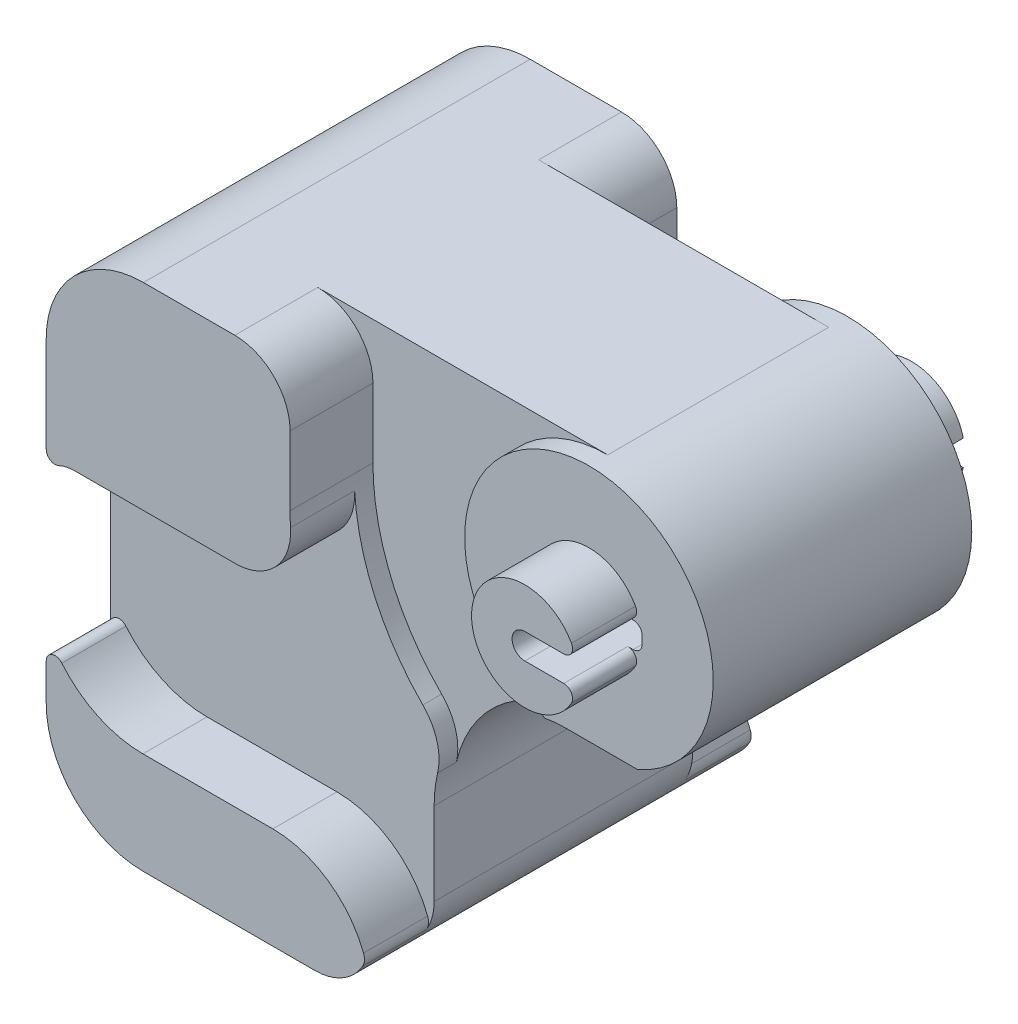
SolidWorks part; units mm, degrees
material "ABS"
ref_plane "Front Plane" through (0, 0, 0) normal (0, 0, 1) x (1, 0, 0)
ref_plane "Top Plane" through (0, 0, 0) normal (0, 1, 0) x (1, 0, 0)
ref_plane "Right Plane" through (0, 0, 0) normal (1, 0, 0) x (0, 0, -1)
sketch "Sketch1" plane through (0, 0, 0) normal (0, 0, 1) x (1, 0, 0)
  line L0 (5.5562, 0) -> (16.6687, 0)
  line L1 (0, 5.5562) -> (22.225, 5.5562)
  line L4 (22.225, 5.5562) -> (22.225, -5.5562) construction
  line L5 (0, 5.5562) -> (22.225, 5.5562) construction
  line L9 (13.1316, 0.7956) -> (22.225, 0) construction
  line L10 (22.225, 0) -> (22.225, -9.1281) construction
  line L11 (5.5562, 0) -> (0, 0)
  line L12 (0, 0) -> (0, 5.5562)
  line L13 (13.7542, 7.9121) -> (13.1316, 0.7956) construction
  circle A0 centre (0, 0) radius 5.5562 construction
  circle A1 centre (22.225, 0) radius 5.5562 construction
  circle A2 centre (22.225, -9.1281) radius 3.5719
  arc A3 (22.225, -5.5562) -> (22.225, 5.5562) centre (22.225, 0) ccw
  circle A5 centre (22.225, 0) radius 1.7859
  circle A6 centre (22.225, -9.1281) radius 1.7859
  arc A7 (16.6687, 0) -> (22.225, -5.5562) centre (22.225, 0) ccw
  circle A23 centre (22.225, 0) radius 9.1281 construction
  circle A30 centre (2.7781, 2.7781) radius 2.7781
  circle A31 centre (0.8137, 4.7426) radius 0.8137
  circle A32 centre (13.1316, 0.7956) radius 1.7859
  circle A33 centre (13.1316, 0.7956) radius 3.5719
  circle A34 centre (13.7542, 7.9121) radius 1.7859
  circle A35 centre (13.7542, 7.9121) radius 3.5719
  arc A36 (14.9108, 0.6399) -> (22.225, -7.3422) centre (22.225, 0) ccw
  arc A37 (22.225, -10.9141) -> (11.3525, 0.9512) centre (22.225, 0) cw
  arc A38 (22.225, -12.7) -> (9.5733, 1.1069) centre (22.225, 0) cw
  dimension "D1" = 22.225
  dimension "D2" = 11.1125
  dimension "D3" = 3.5719
  dimension "D5" = 7.1437
  dimension "D4" = 95
sketch "Sketch3" plane through (0, 0, 0) normal (0, 0, 1) x (1, 0, 0)
  line L0 (0.8137, 5.5562) -> (11.0694, 5.5562)
  line L1 (0, 5.5562) -> (22.225, 5.5562) construction
  line L2 (0, 5.5562) -> (0, 0)
  line L3 (0, 0) -> (9.6495, 0)
  line L4 (5.5562, 0) -> (16.6687, 0) construction
  line L5 (13.1316, 4.6214) -> (15.1433, 4.6214)
  line L7 (0, 0) -> (0, -3.175)
  line L8 (0, -3.175) -> (9.6495, -3.175)
  line L9 (9.6495, -3.175) -> (9.6495, 0)
  line L10 (0, 5.5562) -> (0.8137, 5.5562)
  line L11 (0, 5.5562) -> (0, 11.484)
  line L12 (0, 11.484) -> (13.7542, 11.484)
  line L13 (9.3057, 0.7956) -> (9.3057, -3.175)
  circle A0 centre (13.1316, 0.7956) radius 3.5719
  circle A1 centre (13.7542, 7.9121) radius 3.5719
  circle A2 centre (13.7542, 7.9121) radius 1.5321
  circle A3 centre (13.1316, 0.7956) radius 3.5719 construction
  circle A5 centre (13.7542, 7.9121) radius 3.5719 construction
  circle A6 centre (0.8137, 4.7426) radius 0.8137 construction
  circle A9 centre (13.1316, 0.7956) radius 3.8259
  arc A11 (9.5733, 1.1069) -> (9.6495, -1.7736) centre (22.225, 0) ccw
  dimension "D2" = 3.0643
  dimension "D3" = 0.254
  dimension "D1" = 3.175
extrude "Boss-Extrude1" add sketch "Sketch3" along normal blind 5.5562 contours A1 L12 L11 L10 L0 | A2 | A9 L5 A1 A2 | A9 A1 L0 L10 L2 L3 L13 | L13 L3 L7 L8 region at (5.3993, 8.5885, 0) region at (5.1753, 2.918, 0) region at (10.5911, 9.3448, 0) region at (4.6529, -1.5875, 0) region at (13.7542, 7.9121, 0)
sketch "Sketch5" plane through (0, 0, 5.5562) normal (0, 0, 1) x (1, 0, 0)
  line L0 (13.7542, 11.484) -> (0, 11.484)
  line L1 (0, 11.484) -> (0, -3.175)
  line L2 (0, -3.175) -> (9.3057, -3.175)
  line L3 (9.3057, -3.175) -> (9.3057, 0.7956)
  line L4 (13.7542, 8.2792) -> (15.2864, 8.2792)
  line L5 (15.2864, 8.2792) -> (15.2864, 7.5451)
  line L6 (15.2864, 7.5451) -> (13.7542, 7.5451)
  line L7 (0, 0) -> (9.3057, 0) construction
  line L8 (7.0074, 7.9121) -> (10.1824, 7.9121)
  line L9 (7.0074, 7.9121) -> (7.0074, 11.484)
  line L10 (7.0074, 11.484) -> (10.1824, 11.484)
  line L11 (10.1824, 7.9121) -> (10.1824, 11.484)
  line L12 (5.5562, 0) -> (16.6687, 0) construction
  line L13 (0, 5.5562) -> (7.432, 5.5562) construction
  line L14 (0, 5.5562) -> (22.225, 5.5562) construction
  line L15 (0, -0.254) -> (9.3057, -0.254)
  line L16 (0, 5.8102) -> (7.3431, 5.8102)
  circle A0 centre (13.7542, 7.9121) radius 3.5719
  circle A1 centre (13.1316, 0.7956) radius 3.8259
  circle A2 centre (13.7542, 7.9121) radius 1.5321
  circle A3 centre (13.7542, 7.9121) radius 0.367
  arc A5 (13.1316, 4.6214) -> (9.3057, 0.7956) centre (13.1316, 0.7956) ccw construction
  circle A6 centre (13.7542, 7.9121) radius 6.7469
  circle A7 centre (0.8137, 4.7426) radius 0.8137 construction
  circle A8 centre (2.7781, 2.7781) radius 2.7781 construction
  circle A9 centre (2.7781, 2.7781) radius 2.7781 construction
  circle A10 centre (0.8137, 4.7426) radius 0.8137 construction
  circle A11 centre (2.7781, 2.7781) radius 3.0321
  circle A12 centre (0.8137, 4.7426) radius 1.0677
  circle A14 centre (13.7542, 7.9121) radius 1.5321 construction
  arc M5 (9.3057, 0.7956) -> (13.1316, 4.6214) centre (13.1316, 0.7956) cw
  line M6 (13.1316, 4.6214) -> (15.1433, 4.6214)
  arc M7 (15.1433, 4.6214) -> (13.7542, 11.484) centre (13.7542, 7.9121) ccw
  line M8 (13.7542, 11.484) -> (0, 11.484)
  line M9 (0, 11.484) -> (0, -3.175)
  dimension "D1" = 0.7341
  dimension "D2" = 3.175
  dimension "D3" = 0.254
  dimension "D4" = 0.254
extrude "Cut-Extrude1" cut sketch "Sketch5" against normal blind 1.8415 contours A12 A11 M9 | A11 L15 L3 A6 L16 M5 | A12 A11 L16 | A11 A12 | A11 A12 M9 | A0 A2 L4 L5 L6 M7 M5 M6 | A0 L11 M8 | A12 L1 A11 | A2 L5 L4 | A2 L6 L5 region at (10.9802, 10.6862, 5.5562) region at (16.2096, 10.3675, 5.5562) region at (6.9839, 2.4606, 5.5562) region at (1.6647, 5.7301, 5.5562) region at (2.9672, 2.6346, 5.5562) region at (0.5308, 5.2179, 5.5562) region at (1.0613, 4.4949, 5.5562) region at (0.0057, 4.0253, 5.5562) region at (15.273, 8.1877, 5.5562) region at (15.273, 7.6366, 5.5562)
extrude "Cut-Extrude2" cut sketch "Sketch5<5>" against normal blind 2.3813 contours L8 A6 A1 A0 | L0 A6 L8 L11 | A6 L10 L9 | A0 L11 M8 region at (10.9802, 10.6862, 5.5562) region at (8.7439, 9.5929, 5.5562) region at (9.2585, 5.5769, 5.5562) region at (7.3098, 10.6051, 5.5562)
sketch "Sketch5<5>" plane through (0, 0, 5.5562) normal (0, 0, 1) x (1, 0, 0) same geometry as "Sketch5"
extrude "Cut-Extrude3" cut sketch "Sketch5<6>" against normal through all contours A3 | A3 L6 A2 L4 region at (14.6544, 7.9121, 5.5562) region at (13.7542, 7.9121, 5.5562)
sketch "Sketch5<6>" plane through (0, 0, 5.5562) normal (0, 0, 1) x (1, 0, 0) same geometry as "Sketch5"
mirror "Mirror1" about plane through (0, 0, 0) normal (0, 0, 1) of "Boss-Extrude1", "Cut-Extrude1", "Cut-Extrude2", "Cut-Extrude3"
fillet "Fillet1" radius 2.794 4 edges at (0, 11.484, 0) (0, -3.175, 0) (9.3057, -0.254, -4.6355) (9.3057, -0.254, 4.6355)
fillet "Fillet6" radius 1.5875 1 edges at (9.3057, -3.175, 0)
fillet "Fillet2" radius 1.5875 5 edges at (9.7116, 2.5105, -3.4449) (9.7116, 2.5105, 3.4449) (7.0074, 11.484, -4.3656) (7.0074, 11.484, 4.3656) (7.3431, 5.8102, 4.6355)
fillet "Fillet4" radius 0.254 6 edges at (15.2417, 7.5451, 4.6355) (15.2417, 8.2792, 4.6355) (0, 1.5633, -4.6355) (0, 1.5633, 4.6355) (0, 5.4338, -4.6355) (0, 5.4338, 4.6355)
fillet "Fillet5" radius 0.254 2 edges at (15.2417, 7.5451, 0) (15.2417, 8.2792, 0)
fillet "Fillet7" radius 0.3969 2 edges at (9.1777, -2.212, -4.6355) (9.1777, -2.212, 4.6355)
